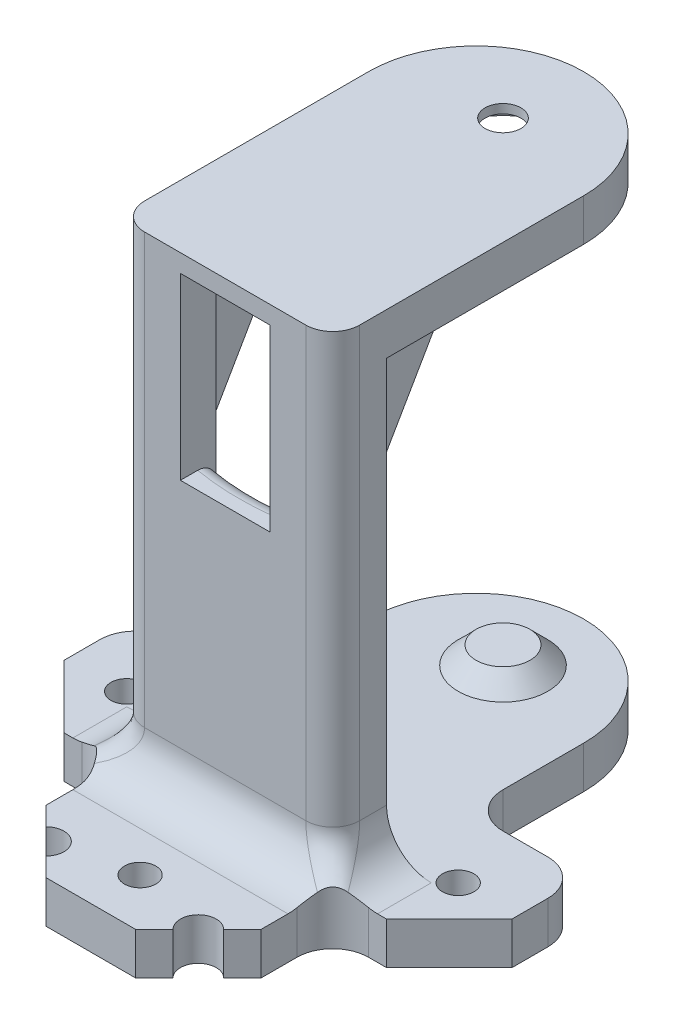
SolidWorks part; units mm, degrees
material "ABS"
ref_plane "Plano frontal" through (0, 0, 0) normal (0, 0, 1) x (1, 0, 0)
ref_plane "Plano superior" through (0, 0, 0) normal (0, 1, 0) x (1, 0, 0)
ref_plane "Plano direito" through (0, 0, 0) normal (1, 0, 0) x (0, 0, -1)
sketch "Esboço3" plane through (0, 0, 0) normal (1, 0, 0) x (0, 0, -1)
  line L0 (0, 0) -> (65, 0)
  line L1 (65, 0) -> (65, 4.7)
  line L2 (65, 4.7) -> (31, 4.7)
  line L3 (31, 4.7) -> (31, 52.9)
  line L4 (31, 52.9) -> (65, 52.9)
  line L5 (65, 52.9) -> (65, 57.6)
  line L6 (65, 57.6) -> (25, 57.6)
  line L7 (25, 57.6) -> (25, 44.6)
  line L8 (25, 44.6) -> (0, 5)
  line L9 (0, 5) -> (0, 0)
  dimension "D1" = 65
  dimension "D2" = 5
  dimension "D3" = 48.2
  dimension "D4" = 4.7
  dimension "D5" = 4.7
  dimension "D6" = 6
  dimension "D8" = 25
  dimension "D9" = 13
extrude "Ressalto-extrusão1" add sketch "Esboço3" along normal blind 24
sketch "Esboço4" plane through (0, 57.6, 0) normal (0, 1, 0) x (1, 0, 0)
  line L0 (24, 0) -> (0, 0) construction
  line L1 (2, 0) -> (22, 0)
  line L2 (2, 0) -> (2, 25)
  line L3 (2, 25) -> (22, 25)
  line L4 (22, 0) -> (22, 25)
  line L5 (0, 25) -> (0, 0) construction
  line L6 (24, 25) -> (24, 0) construction
  line L8 (24, 25) -> (0, 25) construction
  dimension "D1" = 2
  dimension "D2" = 2
extrude "Corte-extrusão1" cut sketch "Esboço4" against normal offset from surface (52.9 mm away) 4.7 up to face at (12, 0, -32.5)
sketch "Esboço5" plane through (0, 4.7, 0) normal (0, 1, 0) x (1, 0, 0)
  line L0 (12, 65) -> (12, 31) construction
  line L1 (12, 56) -> (12, 26.5)
  line L2 (7.5162, 26.1186) -> (5.0252, 55.4068)
  line L3 (16.4838, 26.1186) -> (18.9748, 55.4068)
  line L4 (24, 65) -> (0, 65) construction
  line L5 (24, 31) -> (0, 31) construction
  circle A0 centre (12, 56) radius 2.4
  circle A1 centre (12, 56) radius 2
  arc A2 (5.0252, 55.4068) -> (18.9748, 55.4068) centre (12, 56) cw
  arc A3 (7.5162, 26.1186) -> (16.4838, 26.1186) centre (12, 26.5) ccw
  circle A4 centre (12, 56) radius 27.5
  dimension "D2" = 4.8
  dimension "D3" = 4
  dimension "D4" = 4.5
  dimension "D5" = 7
  dimension "D7" = 55
  dimension "D1" = 9
  dimension "D6" = 29.5
extrude "Corte-extrusão2" [suppressed] cut sketch "Esboço5" against normal through all contours A0
extrude "Corte-extrusão3" cut sketch "Esboço5<3>" along normal up to surface (48.2 mm away) contours A4 up to face at (12, 52.9, -48)
sketch "Esboço5<3>" plane through (0, 4.7, 0) normal (0, 1, 0) x (1, 0, 0) same geometry as "Esboço5"
extrude "Corte-extrusão4" cut sketch "Esboço5<4>" along normal through all contours A1
sketch "Esboço5<4>" plane through (0, 4.7, 0) normal (0, 1, 0) x (1, 0, 0) same geometry as "Esboço5"
extrude "Corte-extrusão5" cut sketch "Esboço5<5>" along direction (0, 1, 0) on the side of the normal blind 2.7 from vertex contours L3 A2 L2 A3 starting at point (24, 52.9, -65)
sketch "Esboço5<5>" plane through (0, 4.7, 0) normal (0, 1, 0) x (1, 0, 0) same geometry as "Esboço5"
fillet "Filete1" radius 12 4 edges at (0, 55.25, -65) (24, 55.25, -65) (24, 2.35, -65) (0, 2.35, -65)
sketch "Esboço6" plane through (0, 4.7, 0) normal (0, 1, 0) x (1, 0, 0)
  circle A0 centre (12, 56) radius 5
  dimension "D1" = 10
extrude "Ressalto-extrusão2" add sketch "Esboço6" along normal blind 2
chamfer "Chanfro1" distance 2 angle 45 1 edges at (12, 6.7, -51)
sketch "Esboço7" plane through (0, 0, -25) normal (0, 0, 1) x (1, 0, 0)
  line L0 (12, 52.9) -> (12, 55.6) construction
  line L1 (7, 55.6) -> (17, 55.6)
  line L2 (7, 55.6) -> (7, 35.6)
  line L3 (7, 35.6) -> (17, 35.6)
  line L4 (17, 55.6) -> (17, 35.6)
  line L5 (7.7574, 52.9) -> (16.2426, 52.9) construction
  line L6 (7.7574, 55.6) -> (16.2426, 55.6) construction
  point P8 (12, 35.6)
  dimension "D1" = 10
  dimension "D2" = 20
extrude "Corte-extrusão6" cut sketch "Esboço7" against normal up to next
fillet "Filete2" radius 2 1 edges at (12, 35.6, -28.5)
sketch "Esboço9" plane through (2, 0, 0) normal (1, 0, 0) x (0, 0, -1)
  line L3 (0, 4.7) -> (25, 4.7)
  line L4 (25, 4.7) -> (25, 44.6)
  line L5 (25, 44.6) -> (0, 5)
  line L6 (0, 4.7) -> (25, 4.7)
  line L7 (25, 4.7) -> (25, 44.6)
  line L8 (25, 44.6) -> (0, 5)
  line L10 (0, 5) -> (0, 4.7)
  line L11 (0, 5) -> (0, 4.7)
  dimension "D1" = 0
extrude "Corte-extrusão7" cut sketch "Esboço9" against normal through all and the other way through all
sketch "Esboço11" plane through (0, 0, 0) normal (0, -1, 0) x (1, 0, 0)
  line L0 (24, 0) -> (24, -53) construction
  line L1 (0, 0) -> (24, 0)
  line L2 (0, 0) -> (0, -10)
  line L3 (0, -10) -> (24, -10)
  line L4 (24, 0) -> (24, -10)
  dimension "D1" = 10
extrude "Corte-extrusão9" cut sketch "Esboço11" against normal blind 10
sketch "Esboço13" plane through (0, 0, 0) normal (0, -1, 0) x (1, 0, 0)
  line L0 (-13, -40) -> (-13, -25)
  line L1 (-13, -40) -> (37, -40)
  line L2 (-13, -25) -> (37, -25)
  line L3 (37, -40) -> (37, -25)
  line L4 (-13, -40) -> (37, -25) construction
  line L5 (-13, -25) -> (37, -40) construction
  line L6 (0, -10) -> (24, -10) construction
  point P1 (12, -32.5)
  point P3 (12, -10)
  dimension "D1" = 50
  dimension "D2" = 15
  dimension "D3" = 15
extrude "Ressalto-extrusão3" add sketch "Esboço13" against normal up to surface (4.7 mm away) up to face at (12, 4.7, -17.5)
fillet "Filete4" radius 4 6 edges at (-13, 2.35, -40) (0, 2.35, -25) (24, 2.35, -25) (37, 2.35, -40) (24, 2.35, -40) (0, 2.35, -40)
fillet "Filete5" radius 5 3 edges at (12, 4.7, -25) (0, 4.7, -28) (24, 4.7, -28)
sketch "Esboço14" plane through (0, 0, 0) normal (0, -1, 0) x (-1, 0, 0)
  line L0 (13, 32.5) -> (-37, 32.5) construction
  line L3 (-12, 10) -> (-12, 65) construction
  line L4 (0, 10) -> (-24, 10) construction
  line L5 (6.5, 25) -> (6.5, 40) construction
  line L8 (0, 15.5) -> (-24, 15.5) construction
  line L9 (0, 10) -> (0, 21) construction
  line L10 (-24, 10) -> (-24, 21) construction
  line L11 (0, 10) -> (-24, 10) construction
  circle A0 centre (6.5, 32.5) radius 1.75
  circle A1 centre (-30.5, 32.5) radius 1.75
  circle A2 centre (-12, 15.5) radius 1.75
  dimension "D1" = 3.5
  dimension "D2" = 22.5
  dimension "D3" = 37
extrude "Corte-extrusão10" cut sketch "Esboço14" against normal blind 10
fillet "Filete6" [suppressed] radius 2
sketch "Esboço16" plane through (0, 0, -25) normal (0, 0, 1) x (1, 0, 0)
  line L0 (12, 57.6) -> (12, 9.7) construction
  line L1 (24, 57.6) -> (0, 57.6) construction
  line L2 (0, 9.7) -> (24, 9.7) construction
  line L3 (5, 55.6) -> (19, 55.6) construction
  line L4 (4.5, 55.6) -> (2.5, 55.6)
  line L5 (4.5, 55.6) -> (4.5, 35.6)
  line L6 (4.5, 35.6) -> (2.5, 35.6)
  line L7 (2.5, 55.6) -> (2.5, 35.6)
  line L8 (0, 57.6) -> (0, 9.7) construction
  line L9 (21.5, 55.6) -> (21.5, 35.6)
  line L10 (19.5, 35.6) -> (21.5, 35.6)
  line L11 (19.5, 55.6) -> (19.5, 35.6)
  line L12 (19.5, 55.6) -> (21.5, 55.6)
  dimension "D1" = 2
  dimension "D2" = 20
  dimension "D3" = 2.5
extrude "Ressalto-extrusão4" add sketch "Esboço16" against normal blind 15
chamfer "Chanfro2" distance 17 angle 30 2 edges at (3.5, 35.6, -40) (20.5, 35.6, -40) first distance on face at (3.5, 44.25, -40) first distance on face at (20.5, 44.25, -40)
chamfer "Chanfro3" distance 7 angle 45 4 edges at (0, 2.35, -10) (24, 2.35, -10) (-13, 2.35, -25) (37, 2.35, -25)
fillet "Filete8" radius 3 4 edges at (24.302, 7.9886, -24.698) (24, 33.65, -25) (-0.302, 7.9886, -24.698) (0, 33.65, -25)
sketch "Esboço17" plane through (0, 0, 0) normal (0, -1, 0) x (1, 0, 0)
  line L0 (7, -10) -> (0, -17) construction
  line L1 (24, -17) -> (17, -10) construction
  circle A0 centre (3.5, -13.5) radius 2
  circle A1 centre (20.5, -13.5) radius 2
  dimension "D1" = 4
extrude "Corte-extrusão11" cut sketch "Esboço17" against normal blind 10 contours A1 | A0
sketch "Esboço18" plane through (0, 55.6, 0) normal (0, -1, 0) x (1, 0, 0)
  arc A0 (5.0252, -55.4068) -> (18.9748, -55.4068) centre (12, -56) ccw construction
  arc A1 (5.0252, -55.4068) -> (18.9748, -55.4068) centre (12, -56) ccw
  arc A2 (18.9748, -55.4068) -> (5, -56) centre (12, -56) ccw
  arc M4 (5.0252, -55.4068) -> (18.9748, -55.4068) centre (12, -56) ccw
  circle M7 centre (12, -56) radius 2
extrude "Corte-extrusão12" cut sketch "Esboço18" against normal blind 1 contours A1 A2 M4 M7 region at (12, 55.6, -49.198)
equation "\"D5@Esboço3\"=\"D4@Esboço3\""
equation "\"D2@Esboço4\"=2"
